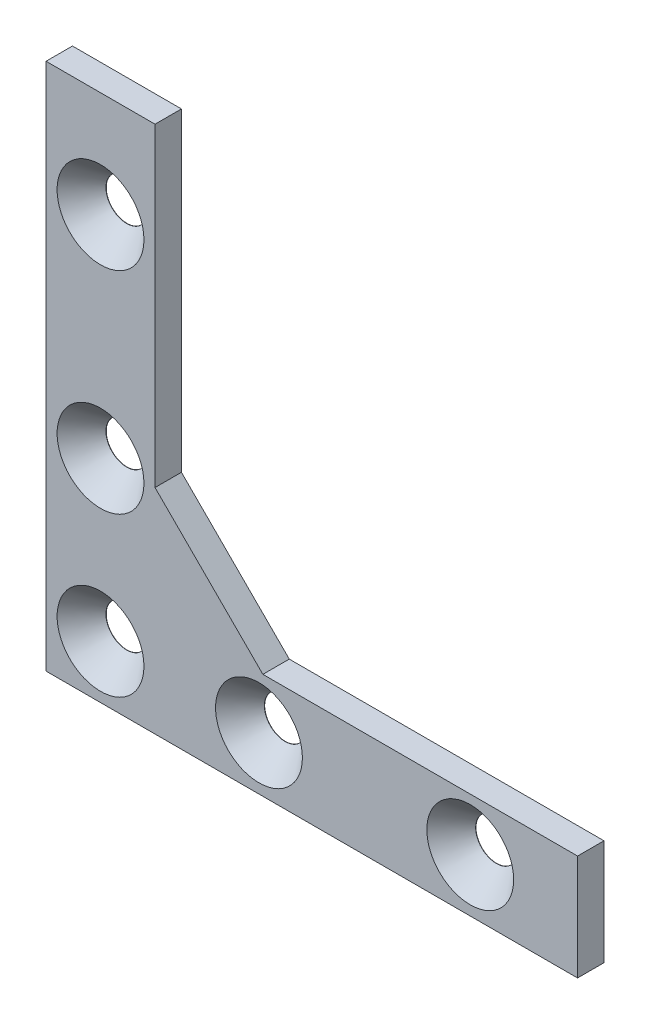
SolidWorks part; units mm, degrees
ref_plane "Front Plane" through (0, 0, 0) normal (0, 0, 1) x (1, 0, 0)
ref_plane "Top Plane" through (0, 0, 0) normal (0, 1, 0) x (1, 0, 0)
ref_plane "Right Plane" through (0, 0, 0) normal (1, 0, 0) x (0, 0, -1)
sketch "Sketch1" plane through (0, 0, 0) normal (0, 0, 1) x (1, 0, 0)
  line L0 (-254, 0) -> (-267.1034, 0)
  line L1 (-267.1034, 0) -> (-267.1034, 63.5)
  line L2 (-267.1034, 63.5) -> (-254, 63.5)
  line L3 (-254, -16.7024) -> (-254, 609.6) construction
  line L4 (-254, 0) -> (-203.2, 0)
  line L6 (-203.2, 0) -> (-203.2, 12.7)
  line L7 (-254, 12.7) -> (254, 12.7) construction
  line L8 (-203.2, 12.7) -> (-241.034, 12.7)
  line L9 (-241.034, 12.7) -> (-254, 25.666)
  line L10 (-254, 25.666) -> (-254, 63.5)
  dimension "D1" = 63.5
  dimension "D2" = 12.7
extrude "Boss-Extrude1" add sketch "Sketch1" along normal blind 3.175
sketch "Sketch2" plane through (0, 0, 3.175) normal (0, 0, 1) x (1, 0, 0)
  line L0 (-260.5517, 63.5) -> (-260.5517, 50.8) construction
  line L1 (-254, 63.5) -> (-267.1034, 63.5) construction
  line L2 (-260.5517, 50.8) -> (-260.5517, 25.4382) construction
  line L3 (-260.5517, 6.3882) -> (-241.5017, 6.3882) construction
  line L4 (-260.5517, 25.4382) -> (-260.5517, 6.3882) construction
  line L5 (-241.5017, 6.3882) -> (-216.1017, 6.3882) construction
  line L6 (-203.2, 6.35) -> (-216.1017, 6.3882) construction
  line L7 (-203.2, 0) -> (-203.2, 12.7) construction
  dimension "D1" = 19.05
  dimension "D2" = 19.05
hole_wizard "#10 Clearance Hole1" positions "Sketch3" profile "Sketch4" hole size "#10" standard "ANSI Inch" end condition through all
sketch "Sketch3" plane through (0, 0, 3.175) normal (0, 0, 1) x (1, 0, 0)
  point P0 (-260.5517, 6.3882)
  point P3 (-260.5517, 25.4382)
  point P6 (-260.5517, 50.8)
  point P9 (-241.5017, 6.3882)
  point P12 (-216.1017, 6.3882)
sketch "Sketch4" plane through (-260.5517, 6.3882, 3.175) normal (1, 0, 0) x (0, -1, 0)
  line L0 (0, 0) -> (0, 3.175)
  line L1 (0, 3.175) -> (2.4892, 3.175)
  line L2 (2.4892, 3.175) -> (2.4892, 3.1411)
  line L3 (2.4892, 3.1411) -> (5.2197, 0)
  line L5 (5.2197, 0) -> (0, 0)
  line L6 (-2.4892, 3.1411) -> (-5.2197, 0) construction
  line L11 (0, -6.35) -> (0, 107.95) construction
  dimension "Thru Hole Dia." = 4.9784
  dimension "Thru Hole Depth" = 3.175
  dimension "Near C'Sink Dia." = 10.4394
  dimension "Near C'Sink Angle" = 82
